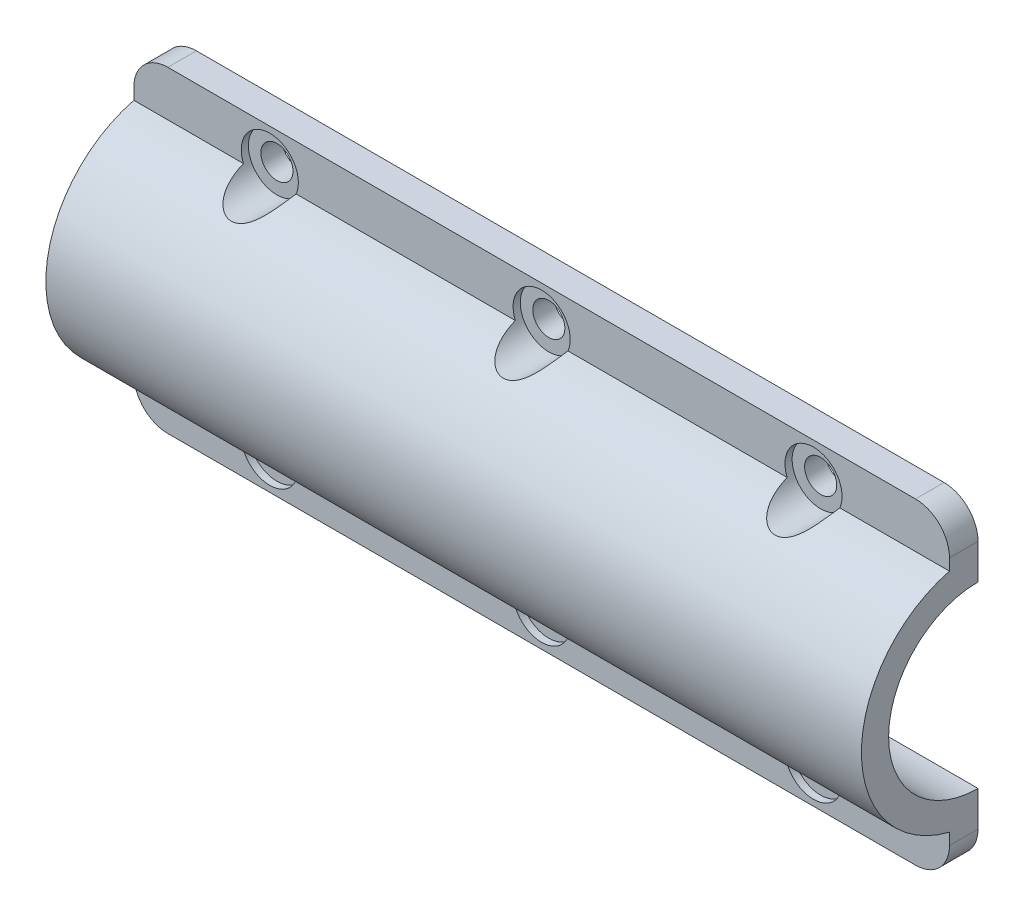
SolidWorks part; units mm, degrees
material "Custom Plastic"
ref_plane "X-Y Datum" through (0, 0, 0) normal (0, 0, 1) x (1, 0, 0)
ref_plane "X-Z Datum" through (0, 0, 0) normal (0, 1, 0) x (1, 0, 0)
ref_plane "Y-Z Datum" through (0, 0, 0) normal (1, 0, 0) x (0, 0, -1)
sketch "Sketch1" plane through (0, 0, 0) normal (1, 0, 0) x (0, 0, -1)
  line L0 (0, 22.225) -> (0, 17.4625) construction
  line L1 (-4, 22.225) -> (-4, 15.8396)
  line L2 (0, -22.225) -> (-4, -22.225)
  line L3 (-4, 11.8711) -> (-4, 11.3422)
  line L4 (-4, -15.8396) -> (-4, -22.225)
  line L7 (23.8125, 12.065) -> (17.8125, 12.065)
  line L8 (23.8125, -17.4625) -> (23.8125, 12.065)
  line L9 (17.8125, 17.4625) -> (0, 17.4625)
  line L10 (0, -12.5269) -> (0, -17.4625)
  line L11 (0, 17.4625) -> (0, 12.5269)
  line L12 (17.8125, 17.4625) -> (0, 17.4625)
  line L13 (17.8125, 12.065) -> (17.8125, 17.4625)
  line L14 (23.8125, 12.065) -> (17.8125, 12.065)
  line L15 (23.8125, -17.4625) -> (23.8125, 12.065)
  line L17 (0, -12.5269) -> (0, -17.4625)
  line L18 (0, 17.4625) -> (0, 12.5269)
  line L20 (17.8125, 12.065) -> (17.8125, 17.4625)
  line L27 (17.8125, 22.225) -> (0, 22.225) construction
  line L28 (17.8125, 22.225) -> (-4, 22.225)
  line L29 (0, 22.225) -> (0, 17.4625)
  line L31 (0, -22.225) -> (23.8125, -22.225) construction
  line L32 (0, -22.225) -> (23.8125, -22.225)
  line L33 (0, -17.4625) -> (23.8125, -17.4625)
  line L34 (0, -17.4625) -> (23.8125, -17.4625)
  line L35 (0, -17.4625) -> (0, -22.225) construction
  line L36 (0, -17.4625) -> (0, -22.225)
  circle A0 centre (0, 0) radius 12.5269
  arc A1 (0, -12.5269) -> (0, 12.5269) centre (0, 0) ccw
  arc A2 (0, -12.5269) -> (0, 12.5269) centre (0, 0) ccw
  circle A3 centre (0, 0) radius 12.0269
  circle A4 centre (0, 0) radius 12.0269
  circle A5 centre (0, 0) radius 16.3369
  dimension "D5" = 4
  dimension "D1" = 0
  dimension "D2" = 0
  dimension "D3" = 0.5
  dimension "D4" = 3.81
extrude "Boss-Extrude1" add sketch "Sketch1" along normal blind 114.3 contours A5 L18 L1 | L18 A5 L17 A0 | A5 L4 L17 region at (0, 19.1968, 2.0273) region at (0, 15.8496, 1.9703) region at (0, -19.1968, 2.0273)
sketch "Sketch2" plane through (0, 0, 4) normal (0, 0, 1) x (1, 0, 0)
  circle A0 centre (19.05, -17.376) radius 4
  circle A1 centre (57.15, -17.376) radius 4
  circle A2 centre (95.25, -17.376) radius 4
  point P0 (19.05, -17.376)
  point P1 (57.15, -17.376)
  point P3 (95.25, -17.376)
  dimension "D1" = 8
extrude "Cut-Extrude1" cut sketch "Sketch2" against normal blind 1 and the other way blind 6.35
hole_wizard "M4 Clearance Hole1" positions "Sketch7" profile "Sketch6" hole size "M4" standard "ANSI Metric" end condition through all
sketch "Sketch7" plane through (0, 0, 4) normal (0, 0, 1) x (1, 0, 0)
  point P0 (19.05, -17.376)
  point P3 (57.15, -17.376)
  point P6 (95.25, -17.376)
sketch "Sketch6" plane through (19.05, -17.376, 4) normal (1, 0, 0) x (0, -1, 0)
  line L0 (0, 0) -> (0, 4)
  line L1 (0, 4) -> (2.25, 4)
  line L2 (2.25, 4) -> (2.25, 0)
  line L5 (2.25, 0) -> (0, 0)
  line L11 (0, -6.35) -> (0, 107.95) construction
  dimension "Thru Hole Dia." = 4.5
  dimension "Thru Hole Depth" = 4
mirror "Mirror1" about plane through (0, 0, 0) normal (0, 1, 0) of "M4 Clearance Hole1", "Cut-Extrude1"
fillet "Fillet1" radius 4.7625 4 edges at (114.3, 22.225, 2) (114.3, -22.225, 2) (0, 22.225, 2) (0, -22.225, 2)
